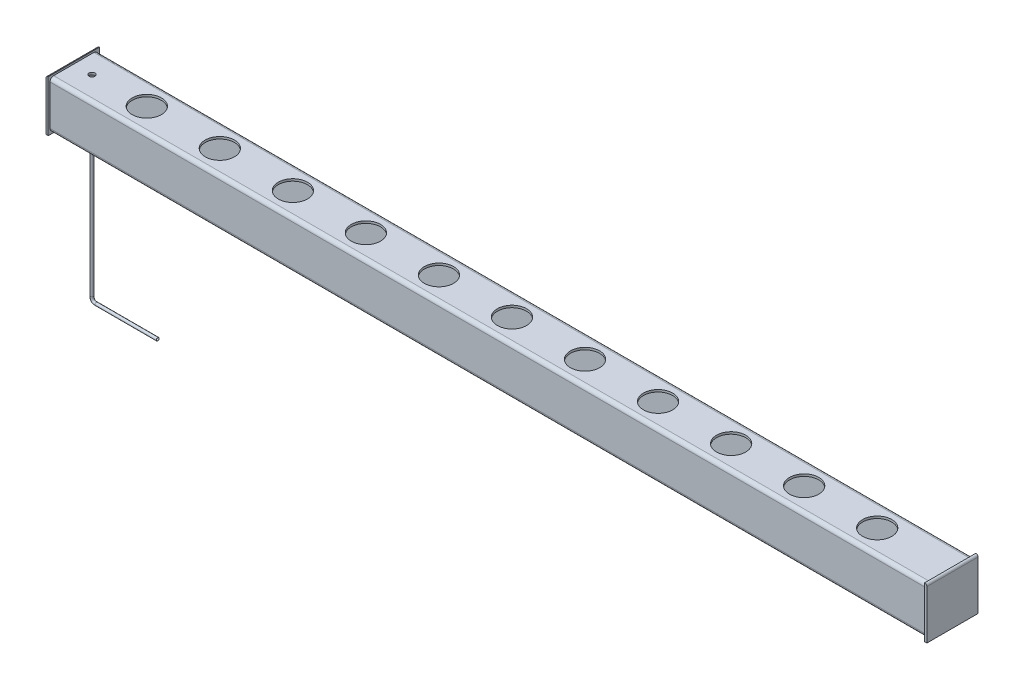
SolidWorks part; units mm, degrees
ref_plane "Front Plane" through (0, 0, 0) normal (0, 0, 1) x (1, 0, 0)
ref_plane "Top Plane" through (0, 0, 0) normal (0, 1, 0) x (1, 0, 0)
ref_plane "Right Plane" through (0, 0, 0) normal (1, 0, 0) x (0, 0, -1)
sketch "Sketch1" plane through (0, 0, 0) normal (1, 0, 0) x (0, 0, -1)
  line L1 (-32.5, -32.5) -> (32.5, -32.5)
  line L2 (-32.5, -32.5) -> (-32.5, 32.5)
  line L3 (-32.5, 32.5) -> (32.5, 32.5)
  line L4 (32.5, -32.5) -> (32.5, 32.5)
  line L5 (-32.5, -32.5) -> (32.5, 32.5) construction
  line L6 (-32.5, 32.5) -> (32.5, -32.5) construction
  point P0 (0, 0)
  dimension "D1" = 65
extrude "Boss-Extrude2" add sketch "Sketch1" along normal mid plane 1200
fillet "Fillet1" radius 5 4 edges at (0, -32.5, -32.5) (0, -32.5, 32.5) (0, 32.5, -32.5) (0, 32.5, 32.5)
shell "Shell1" thickness 3 removed face at (-600, 0, 0) removed face at (600, 0, 0)
sketch "Sketch2" plane through (600, 0, 0) normal (1, 0, 0) x (0, 0, -1)
  line L1 (-35, -35) -> (35, -35)
  line L2 (-35, -35) -> (-35, 35)
  line L3 (-35, 35) -> (35, 35)
  line L4 (35, -35) -> (35, 35)
  line L5 (-35, -35) -> (35, 35) construction
  line L6 (-35, 35) -> (35, -35) construction
  point P0 (0, 0)
  dimension "D1" = 70
extrude "Boss-Extrude3" add sketch "Sketch2" along normal blind 3 separate body
fillet "Fillet4" radius 3 1 edges at (603, 35, 0)
mirror "Mirror1" about plane through (0, 0, 0) normal (1, 0, 0) of bodies 103
sketch "Sketch3" plane through (0, 32.5, 0) normal (0, 1, 0) x (1, 0, 0)
  circle A0 centre (0, 0) radius 20
  dimension "D1" = 40
extrude "Cut-Extrude1" cut sketch "Sketch3" against normal up to next (3 mm away)
pattern_linear "LPattern1" count 6 spacing 100 along (-1, 0, 0) count 6 spacing 100 along (1, 0, 0) of "Cut-Extrude1"
sketch "Sketch4" plane through (0, 32.5, 0) normal (0, 1, 0) x (1, 0, 0)
  circle A0 centre (-575, 0) radius 4
  circle A1 centre (-575, 0) radius 2
  circle A3 centre (-575, 0) radius 1.75
  circle A4 centre (-500, 0) radius 20 construction
  point P3 (-571.6144, 0)
  dimension "D1" = 8
  dimension "D2" = 4
  dimension "D3" = 75
  dimension "D4" = 0.25
extrude "Cut-Extrude2" cut sketch "Sketch4" against normal up to next (3 mm away) contours A1 | A0 A1 | A3 region at (-578.8869, 32.5, 0) region at (-576.9434, 32.5, 0) region at (-575, 32.5, 0)
extrude "Cut-Extrude3" cut sketch "Sketch4<3>" against normal through all contours A1
sketch "Sketch4<3>" plane through (0, 32.5, 0) normal (0, 1, 0) x (1, 0, 0) same geometry as "Sketch4"
extrude "Boss-Extrude4" add sketch "Sketch4<4>" along normal blind 10 and the other way blind 200 from surface separate body contours A1 A3 region at (-576.9434, 32.5, 0) starting at face at (-575, -29.5, 2)
sketch "Sketch4<4>" plane through (0, 32.5, 0) normal (0, 1, 0) x (1, 0, 0) same geometry as "Sketch4"
sketch "Sketch5" plane through (0, 0, 0) normal (0, 0, 1) x (1, 0, 0)
  line L0 (-575, -229.5) -> (-575, -236.2359) construction
  line L1 (-577, -229.5) -> (-573, -229.5) construction
  line L2 (-569.0493, -236.2359) -> (-485, -236.2359)
  line L3 (-364.6239, -236.2359) -> (-371.982, -236.2359) construction
  line L4 (-575, -232.8624) -> (-575, -225.775) construction
  line L5 (-575, -236.2359) -> (-569.0493, -236.2359) construction
  spline S0 degree 3 poles (-575, -229.5) (-575, -236.1071) (-572.1152, -236.2359) (-569.0493, -236.2359) knots 0 0 0 0 1 1 1 1
  point P10 (-569.0493, -236.2359)
  dimension "D1" = 90
sketch "Sketch6" plane through (0, -229.5, 0) normal (0, -1, 0) x (1, 0, 0)
  circle A0 centre (-575, 0) radius 1.75 construction
  circle A1 centre (-575, 0) radius 2
  circle A2 centre (-575, 0) radius 2
  circle A3 centre (-575, 0) radius 1.75
  dimension "D1" = 0
sweep "Sweep1" add profiles "Sketch6" path "Sketch5"
